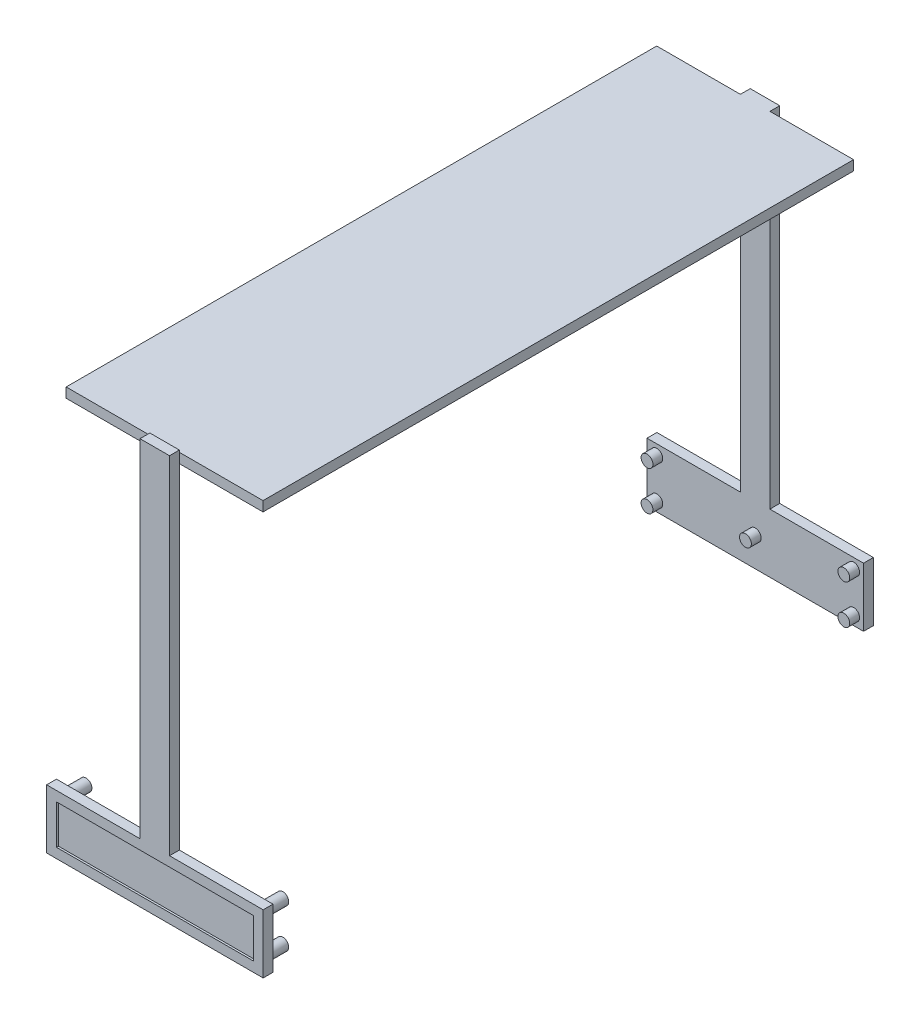
SolidWorks part; units mm, degrees
note: The reader was unsure of these and kept them because the rebuilt part matched: shared geometry of "Sketch3<10>", "3DSketch4<4>".
ref_plane "Front Plane" through (0, 0, 0) normal (0, 0, 1) x (1, 0, 0)
ref_plane "Top Plane" through (0, 0, 0) normal (0, 1, 0) x (1, 0, 0)
ref_plane "Right Plane" through (0, 0, 0) normal (1, 0, 0) x (0, 0, -1)
sketch "Sketch2" plane through (0, 0, 0) normal (0, 0, 1) x (1, 0, 0)
  line L1 (55, -15) -> (-55, -15)
  line L2 (55, -15) -> (55, 15)
  line L3 (55, 15) -> (-55, 15)
  line L4 (-55, -15) -> (-55, 15)
  line L5 (55, -15) -> (-55, 15) construction
  line L6 (55, 15) -> (-55, -15) construction
  line L7 (50, -10) -> (-50, -10)
  line L8 (50, -10) -> (50, 10)
  line L9 (50, 10) -> (-50, 10)
  line L10 (-50, -10) -> (-50, 10)
  line L11 (50, -10) -> (-50, 10) construction
  line L12 (50, 10) -> (-50, -10) construction
  point P1 (0, 0)
  point P6 (0, 0)
  dimension "D1" = 30
  dimension "D2" = 110
  dimension "D3" = 100
  dimension "D4" = 20
extrude "Boss-Extrude1" add sketch "Sketch2" along normal blind 5
sketch "Sketch3" plane through (0, 15, 0) normal (0, 1, 0) x (1, 0, 0)
  line L0 (55, 0) -> (-55, 0) construction
  line L1 (55, -5) -> (55, 0) construction
  line L2 (55, 0) -> (55, -5)
  line L3 (7.4317, -5) -> (-7.5683, -5)
  line L4 (7.4317, -5) -> (7.4317, 0)
  line L5 (7.4317, 0) -> (-7.5683, 0)
  line L6 (-7.5683, -5) -> (-7.5683, 0)
  line L7 (7.4317, -5) -> (-7.5683, 0) construction
  line L8 (7.4317, 0) -> (-7.5683, -5) construction
  circle A0 centre (-0.0683, -2.5) radius 2.4467
  circle A4 centre (4.9317, -2.5) radius 2.4467
  circle A5 centre (-5.0683, -2.5) radius 2.4467
  dimension "D1" = 2
  dimension "D2" = 2
  dimension "D3" = 15
extrude "Cut-Extrude3" cut sketch "Sketch3" against normal blind 15 contours A4 | A0 | A5
extrude "Boss-Extrude4" add sketch "Sketch3<10>" along normal blind 175 contours A4 | A5 | L5 L6 L3 L4 | A0
sketch "Sketch3<10>" plane through (0, 15, 0) normal (0, 1, 0) x (1, 0, 0) same geometry as "Sketch3"
sketch "Sketch5" plane through (0, 0, 0) normal (0, 0, -1) x (-1, 0, 0)
  line L0 (7.5683, 190) -> (7.5683, 15) construction
  line L1 (-7.4317, 190) -> (7.5683, 190)
  line L2 (-7.4317, 190) -> (-7.4317, 185)
  line L3 (-7.4317, 185) -> (7.5683, 185)
  line L4 (7.5683, 190) -> (7.5683, 185)
  dimension "D1" = 5
sketch "Sketch12" plane through (0, 0, 0) normal (0, 0, -1) x (-1, 0, 0)
  line L1 (-50, 10) -> (50, 10)
  line L2 (-50, 10) -> (-50, -10)
  line L3 (-50, -10) -> (50, -10)
  line L4 (50, 10) -> (50, -10)
extrude "Boss-Extrude12" add sketch "Sketch12" against normal blind 1 contours L2 L1 L4 L3
extrude "Boss-Extrude13" add sketch "Sketch5" along normal blind 300
sketch "Sketch13" plane through (0, 0, -300) normal (0, 0, -1) x (-1, 0, 0)
  line L0 (-7.4317, 190) -> (7.5683, 185) construction
  line L1 (-7.4317, 185) -> (7.5683, 190) construction
  circle A0 centre (0.0683, 187.5) radius 2
  circle A1 centre (5.0683, 187.5) radius 2
  circle A2 centre (0.0683, 187.5) radius 2
  circle A3 centre (-4.9317, 187.5) radius 2
  dimension "D1" = 2
  dimension "D2" = 2
extrude "Cut-Extrude10" cut sketch "Sketch13" against normal blind 301 contours A3 | A0 | A1
sketch3d "3DSketch1"
  line L0 (-7.5683, 190, -300) -> (7.4317, 190, -300)
  line L1 (7.4317, 190, -300) -> (7.4317, 190, -305)
  line L2 (-7.5683, 190, -300) -> (-7.5683, 190, -305)
  line L3 (-7.5683, 190, -305) -> (7.4317, 190, -305)
  dimension "D1" = 5
  dimension "D2" = 5
extrude "Boss-Extrude16" add sketch "3DSketch1" along direction (0, 1, 0) on the side of the normal blind 205
sketch "Sketch15" plane through (0, 0, -305) normal (0, 0, -1) x (-1, 0, 0)
  line L0 (-7.4317, 15) -> (7.5683, -15)
  line L1 (-7.4317, -15) -> (7.5683, 15)
  line L2 (7.5683, 190) -> (7.5683, -15) construction
  line L4 (25, -8.8521) -> (-25, -8.8521)
  line L5 (25, -8.8521) -> (25, 8.8521)
  line L6 (25, 8.8521) -> (-25, 8.8521)
  line L7 (-25, -8.8521) -> (-25, 8.8521)
  line L8 (25, -8.8521) -> (-25, 8.8521) construction
  line L9 (25, 8.8521) -> (-25, -8.8521) construction
  point P9 (0, 0)
  dimension "D1" = 50
sketch "Sketch22" plane through (0, 0, 0) normal (0, 0, -1) x (-1, 0, 0)
  line L1 (50, -10) -> (-50, -10)
  line L2 (50, -10) -> (50, 10)
  line L3 (50, 10) -> (-50, 10)
  line L4 (-50, -10) -> (-50, 10)
  line L5 (50, -10) -> (-50, 10) construction
  line L6 (50, 10) -> (-50, -10) construction
  circle A0 centre (50, 10) radius 3
  circle A1 centre (50, -10) radius 3
  circle A2 centre (0, 0) radius 3
  circle A3 centre (-50, 10) radius 3
  circle A4 centre (-50, -10) radius 3
  point P0 (0, 0)
  dimension "D3" = 6
  dimension "D1" = 100
  dimension "D2" = 20
extrude "Boss-Extrude20" add sketch "Sketch22" along normal blind 10 contours L4 A4 L1 | L1 A4 L4 | A2 | A3 | A0 | A1
sketch "Sketch26" plane through (0, 0, -305) normal (0, 0, -1) x (-1, 0, 0)
  line L1 (55, -15) -> (-55, -15)
  line L2 (55, -15) -> (55, 15)
  line L3 (55, 15) -> (-55, 15)
  line L4 (-55, -15) -> (-55, 15)
  line L5 (55, -15) -> (-55, 15) construction
  line L6 (55, 15) -> (-55, -15) construction
  point P0 (0, 0)
extrude "Boss-Extrude22" add sketch "Sketch26" against normal blind 5
sketch "Sketch27" plane through (0, 0, -300) normal (0, 0, 1) x (1, 0, 0)
  line L1 (50, -10) -> (-50, -10)
  line L2 (50, -10) -> (50, 10)
  line L3 (50, 10) -> (-50, 10)
  line L4 (-50, -10) -> (-50, 10)
  line L5 (50, -10) -> (-50, 10) construction
  line L6 (50, 10) -> (-50, -10) construction
  circle A0 centre (0, 0) radius 3
  circle A1 centre (-50, 10) radius 3
  circle A2 centre (-50, -10) radius 3
  circle A3 centre (50, 10) radius 3
  circle A4 centre (50, -10) radius 3
  point P0 (0, 0)
  dimension "D1" = 100
  dimension "D2" = 20
extrude "Boss-Extrude23" add sketch "Sketch27" along normal blind 5 contours A1 | A2 | A0 | A3 | A4
sketch "Sketch28" plane through (0, 185, 0) normal (0, -1, 0) x (1, 0, 0)
  line L0 (12.7317, -219) -> (12.7317, -251)
  line L6 (12.7317, -134) -> (-12.2683, -134)
  line L7 (13.9317, -132.5) -> (-14.0683, -132.5)
  line L8 (13.9317, -132.5) -> (13.9317, -167.5)
  line L9 (13.9317, -167.5) -> (-14.0683, -167.5)
  line L10 (-14.0683, -132.5) -> (-14.0683, -167.5)
  line L11 (12.7317, -219) -> (-12.2683, -219)
  line L12 (-12.2683, -219) -> (-12.2683, -251)
  line L13 (12.7317, -134) -> (12.7317, -166)
  line L14 (12.7317, -166) -> (-12.2683, -166)
  line L15 (-12.2683, -134) -> (-12.2683, -166)
  line L16 (12.7317, -134) -> (-12.2683, -166) construction
  line L17 (12.7317, -166) -> (-12.2683, -134) construction
  line L18 (12.7317, -251) -> (-12.2683, -251)
  line L19 (13.9317, -217.5) -> (13.9317, -252.5)
  line L20 (13.9317, -217.5) -> (-14.0683, -217.5)
  line L21 (-14.0683, -217.5) -> (-14.0683, -252.5)
  line L22 (13.9317, -252.5) -> (-14.0683, -252.5)
  line L23 (12.7317, -134) -> (12.7317, -166)
  line L24 (12.7317, -134) -> (-12.2683, -134)
  line L25 (-12.2683, -134) -> (-12.2683, -166)
  line L26 (12.7317, -166) -> (-12.2683, -166)
  line L27 (13.9317, -132.5) -> (13.9317, -167.5)
  line L28 (13.9317, -132.5) -> (-14.0683, -132.5)
  line L29 (-14.0683, -132.5) -> (-14.0683, -167.5)
  line L30 (13.9317, -167.5) -> (-14.0683, -167.5)
  line L31 (12.7317, -49) -> (12.7317, -81)
  line L32 (12.7317, -49) -> (-12.2683, -49)
  line L33 (-12.2683, -49) -> (-12.2683, -81)
  line L34 (12.7317, -81) -> (-12.2683, -81)
  line L35 (13.9317, -47.5) -> (13.9317, -82.5)
  line L36 (13.9317, -47.5) -> (-14.0683, -47.5)
  line L37 (-14.0683, -47.5) -> (-14.0683, -82.5)
  line L38 (13.9317, -82.5) -> (-14.0683, -82.5)
  point P0 (0.2317, -150)
  point P6 (-0.0683, -150)
  dimension "D1" = 35
  dimension "D2" = 28
  dimension "D3" = 32
  dimension "D4" = 25
  dimension "D5" = 2
  dimension "D6" = 2
extrude "Boss-Extrude26" add sketch "Sketch28" along normal blind 7 contours L22 L19 L20 L6 L11 L0 L18 | L8 L9 L10 L7 | L35 L38 L37 L36 | L31 L34 L33 L32
sketch3d "3DSketch4"
  line L1 (-7.5683, 190, 5) -> (-7.5683, 190, -305) construction
  line L4 (-7.5683, 185, -300) -> (-7.5683, 190, -300)
  line L5 (-7.5683, 185, -300) -> (-7.5683, 185, 0)
  line L6 (-7.5683, 185, 0) -> (-7.5683, 190, 0)
  line L7 (-7.5683, 190, -300) -> (-7.5683, 190, 0)
extrude "Boss-Extrude28" add sketch "3DSketch4" along direction (1, 0, 0) on the side of the normal blind 42.5 contours L5 L4 L7 L6
extrude "Boss-Extrude29" add sketch "3DSketch4<4>" along direction (1, 0, 0) on the side against the normal blind 57.5
sketch3d "3DSketch4<4>" same geometry as "3DSketch4"
sketch3d "3DSketch5"
  line L1 (-7.5683, 190, 5) -> (-7.5683, 190, 0)
  line L2 (-7.5683, 190, 5) -> (7.4317, 190, 5)
  line L3 (7.4317, 190, 5) -> (7.4317, 190, 0)
  line L4 (-7.5683, 190, 0) -> (7.4317, 190, 0)
extrude "Boss-Extrude30" add sketch "3DSketch5" along direction (0, 1, 0) on the side of the normal blind 1
sketch "Sketch30" plane through (0, 185, 0) normal (0, -1, 0) x (1, 0, 0)
  line L1 (10.4622, -136.905) -> (-9.8478, -136.905)
  line L2 (10.4622, -136.905) -> (10.4622, -163.095)
  line L3 (10.3867, -222.0016) -> (-9.9233, -222.0016)
  line L4 (10.3867, -222.0016) -> (10.3867, -248.1916)
  line L5 (10.3867, -248.1916) -> (-9.9233, -248.1916)
  line L6 (-9.9233, -222.0016) -> (-9.9233, -248.1916)
  line L7 (10.3867, -222.0016) -> (-9.9233, -248.1916) construction
  line L8 (10.3867, -248.1916) -> (-9.9233, -222.0016) construction
  line L13 (10.4622, -51.905) -> (-9.8478, -51.905)
  line L14 (10.4622, -51.905) -> (10.4622, -78.095)
  line L15 (10.4622, -163.095) -> (-9.8478, -163.095)
  line L16 (-9.8478, -136.905) -> (-9.8478, -163.095)
  line L23 (10.4622, -136.905) -> (-9.8478, -163.095) construction
  line L24 (10.4622, -163.095) -> (-9.8478, -136.905) construction
  line L25 (10.4622, -78.095) -> (-9.8478, -78.095)
  line L26 (-9.8478, -51.905) -> (-9.8478, -78.095)
  line L27 (10.4622, -51.905) -> (-9.8478, -78.095) construction
  line L28 (10.4622, -78.095) -> (-9.8478, -51.905) construction
  circle A0 centre (-9.9233, -248.1916) radius 0.6
  circle A1 centre (10.3867, -248.1916) radius 0.6
  circle A2 centre (-9.9233, -222.0016) radius 0.6
  circle A3 centre (10.3867, -222.0016) radius 0.6
  circle A4 centre (10.4622, -163.095) radius 0.6
  circle A5 centre (-9.8478, -163.095) radius 0.6
  circle A6 centre (-9.8478, -136.905) radius 0.6
  circle A7 centre (10.4622, -136.905) radius 0.6
  circle A8 centre (10.4622, -51.905) radius 0.6
  circle A9 centre (-9.8478, -51.905) radius 0.6
  circle A10 centre (-9.8478, -78.095) radius 0.6
  circle A11 centre (10.4622, -78.095) radius 0.6
  point P2 (0.3072, -65)
  point P8 (0.2317, -235.0966)
  point P17 (0.2317, -150)
  point P26 (0.2317, -65)
  point P27 (0.3072, -150)
  dimension "D3" = 1.2
  dimension "D4" = 26.19
  dimension "D8" = 1.2
  dimension "D9" = 1.2
  dimension "D10" = 1.2
  dimension "D11" = 1.2
  dimension "D12" = 1.2
  dimension "D13" = 1.2
  dimension "D14" = 1.2
  dimension "D15" = 1.2
  dimension "D16" = 1.2
  dimension "D17" = 1.2
  dimension "D18" = 1.2
  dimension "D1" = 20.31
  dimension "D2" = 26.19
  dimension "D5" = 20.31
  dimension "D6" = 26.19
  dimension "D7" = 20.31
extrude "Boss-Extrude32" add sketch "Sketch30" along normal blind 7.5 contours A1 | A0 | A2 | A3 | A5 | A4 | A7 | A6 | A10 | A11 | A8 | A9
sketch3d "3DSketch6"
  line L1 (-50, 10, 1) -> (50, 10, 1)
  line L2 (-50, 10, 1) -> (-50, -10, 1)
  line L3 (-50, -10, 1) -> (50, -10, 1)
  line L4 (50, 10, 1) -> (50, -10, 1)
extrude "Boss-Extrude34" add sketch "3DSketch6" along direction (0, 0, 1) on the side of the normal blind 3
equation "\"42.5.00mm\"=30"
